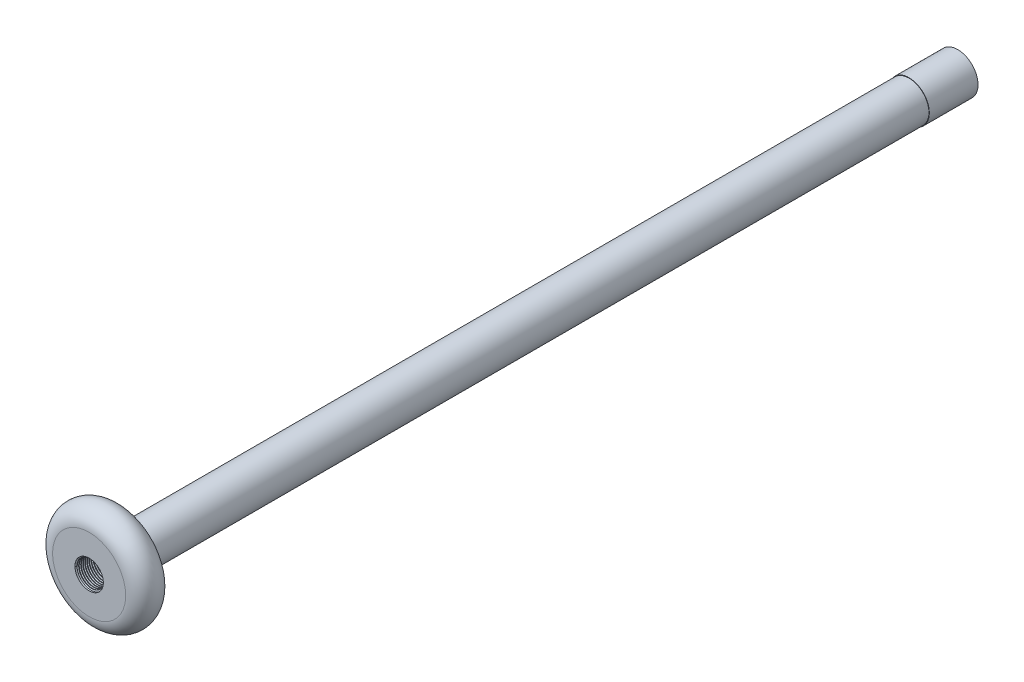
SolidWorks part; units mm, degrees
material "6061 Alloy"
ref_plane "Front Plane" through (0, 0, 0) normal (0, 0, 1) x (1, 0, 0)
ref_plane "Top Plane" through (0, 0, 0) normal (0, 1, 0) x (1, 0, 0)
ref_plane "Right Plane" through (0, 0, 0) normal (1, 0, 0) x (0, 0, -1)
sketch "Sketch1" plane through (0, 0, 0) normal (0, 0, 1) x (1, 0, 0)
  circle A0 centre (0, 0) radius 2.45
  dimension "D1" = 4.9
extrude "Boss-Extrude1" add sketch "Sketch1" along normal blind 101
sketch "Sketch2" plane through (0, 0, 101) normal (0, 0, 1) x (1, 0, 0)
  circle A0 centre (0, 0) radius 6.5
  dimension "D1" = 13
extrude "Boss-Extrude2" add sketch "Sketch2" against normal blind 4
fillet "Fillet2" 2 edges at (6.5, 0, 97) (6.5, 0, 101) type full round first side face at (2.45, 0, 97) second side face at (6.5, 0, 101) middle face at (6.5, 0, 97)
sketch "Sketch3" plane through (0, 0, 101) normal (0, 0, 1) x (1, 0, 0)
  circle A0 centre (0, 0) radius 1.75
  dimension "D1" = 3.5
extrude "Cut-Extrude1" cut sketch "Sketch3" against normal blind 10
thread "Thread1" pitch 0.25 method extrude profile "Thread Profile1" start angle 0, offset 0, length 10, pitch 0.25, diameter 3.5
ref_plane "Plane1" through (-1.75, 0, 101) normal (0, -1, 0) x (-1, 0, 0)
sketch "Thread Profile1" plane through (-1.75, 0, 101) normal (0, -1, 0) x (-1, 0, 0)
  line L0 (0, 0) -> (0, 0.25) construction
  line L11 (0, 0) -> (0, 0.2187)
  line L12 (0, 0.2187) -> (-0.1353, 0.1406)
  line L13 (-0.1353, 0.1406) -> (-0.1353, 0.0781)
  line L15 (-0.1353, 0.0781) -> (0, 0)
  line L17 (-0.1353, 0.1094) -> (0, 0.1094) construction
  point P2 (0, 0)
  dimension "Pitch" = 0.25
  dimension "Profile_Angle" = 60
  dimension "Profile_Land" = 0.0625
  dimension "Profile_Height" = 0.1353
sketch "Sketch7" plane through (0, 0, 0) normal (0, 0, -1) x (-1, 0, 0)
  circle A0 centre (0, 0) radius 2.5
  dimension "D1" = 5
extrude "Boss-Extrude3" add sketch "Sketch7" along normal blind 6
